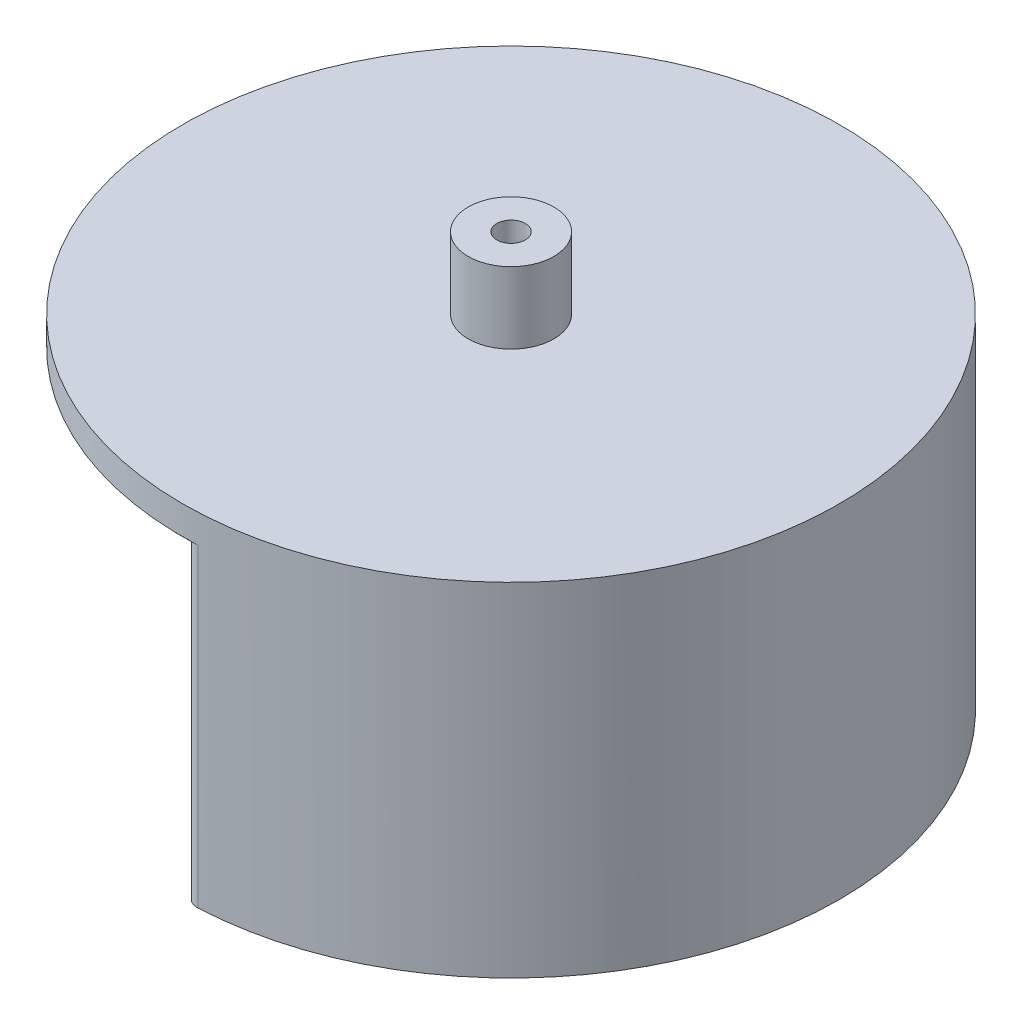
SolidWorks part; units mm, degrees
ref_plane "Front Plane" through (0, 0, 0) normal (0, 0, 1) x (1, 0, 0)
ref_plane "Top Plane" through (0, 0, 0) normal (0, 1, 0) x (1, 0, 0)
ref_plane "Right Plane" through (0, 0, 0) normal (1, 0, 0) x (0, 0, -1)
sketch "Sketch1" plane through (0, 0, 0) normal (0, 1, 0) x (1, 0, 0)
  circle A0 centre (0, 0) radius 23
  dimension "D1" = 46
extrude "Boss-Extrude1" add sketch "Sketch1" along normal blind 24
sketch "Sketch3" plane through (0, 0, 0) normal (1, 0, 0) x (0, 0, -1)
  line L0 (0, 0.5522) -> (-23, 22)
  line L3 (-23, 22) -> (0, 22) construction
  line L4 (0, 22) -> (0, 0.5522) construction
  line L6 (-23, 24) -> (-23, 0) construction
  line L7 (0, 0) -> (0, 24) construction
  line L8 (-23, 0) -> (23, 0) construction
  line L9 (23, 24) -> (-23, 24) construction
  line L10 (-23, 22) -> (-23, 0)
  line L11 (-23, 0) -> (0, 0)
  line L12 (0, 0) -> (0, 0.5522)
  dimension "D1" = 43
  dimension "D2" = 2
revolve "Cut-Revolve1" cut sketch "Sketch3" angle 180 about L4
sketch "Sketch4" plane through (0, 0, 0) normal (0, -1, 0) x (1, 0, 0)
  line L2 (2, 20.9045) -> (2, -20.9045)
  line L3 (2, 20.9045) -> (2, -20.9045)
  arc A2 (2, -20.9045) -> (2, 20.9045) centre (0, 0) ccw
  arc A3 (2, -20.9045) -> (2, 20.9045) centre (0, 0) ccw
  dimension "D1" = 2
extrude "Cut-Extrude2" cut sketch "Sketch4" against normal offset from surface (22 mm away) 2 up to face at (0, 24, 23)
sketch "Sketch5" plane through (0, 24, 0) normal (0, 1, 0) x (1, 0, 0)
  circle A0 centre (0, 0) radius 1
  dimension "D1" = 2
extrude "Cut-Extrude3" cut sketch "Sketch5" against normal through all
fillet "Fillet1" radius 1 6 edges at (0, 0.7423, -1) (0, 0.7423, 1) (1, 0, 0) (-1, 1.4847, 0) (0, 11, 23) (0, 11, -23)
sketch "Sketch6" plane through (0, 24, 0) normal (0, 1, 0) x (1, 0, 0)
  circle A0 centre (0, 0) radius 1
  circle A1 centre (0, 0) radius 3
  circle A2 centre (0, 0) radius 1 construction
  dimension "D1" = 6
extrude "Boss-Extrude2" add sketch "Sketch6" along normal blind 5
